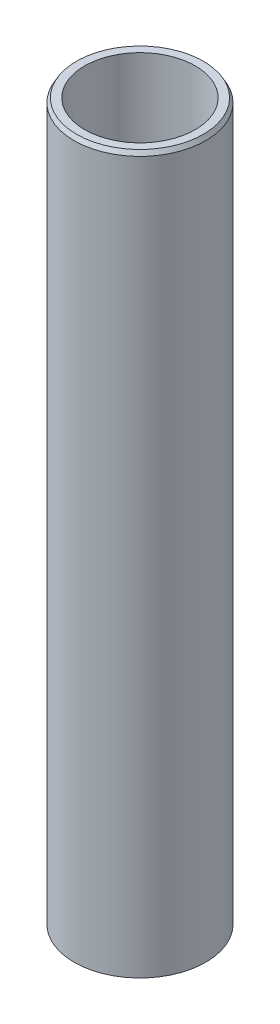
SolidWorks part; units mm, degrees
ref_plane "Front Plane" through (0, 0, 0) normal (0, 0, 1) x (1, 0, 0)
ref_plane "Top Plane" through (0, 0, 0) normal (0, 1, 0) x (1, 0, 0)
ref_plane "Right Plane" through (0, 0, 0) normal (1, 0, 0) x (0, 0, -1)
sketch "Sketch1" plane through (0, 0, 0) normal (0, 1, 0) x (1, 0, 0)
  circle A0 centre (0, 0) radius 55
  dimension "SHAFT_OD" = 110
extrude "Boss-Extrude1" add sketch "Sketch1" along normal blind 600
sketch "Sketch2" plane through (0, 0, 0) normal (0, 1, 0) x (1, 0, 0)
  circle A0 centre (0, 0) radius 46.1978
  dimension "BORE_D" = 92.3955
extrude "Cut-Extrude1" cut sketch "Sketch2" along normal through all
chamfer "Chamfer1" distance 3.5531 angle 30 2 edges at (0, 600, 55) (0, 0, 55) first distance on face at (0, 600, 55) first distance on face at (0, 0, 46.1978)
